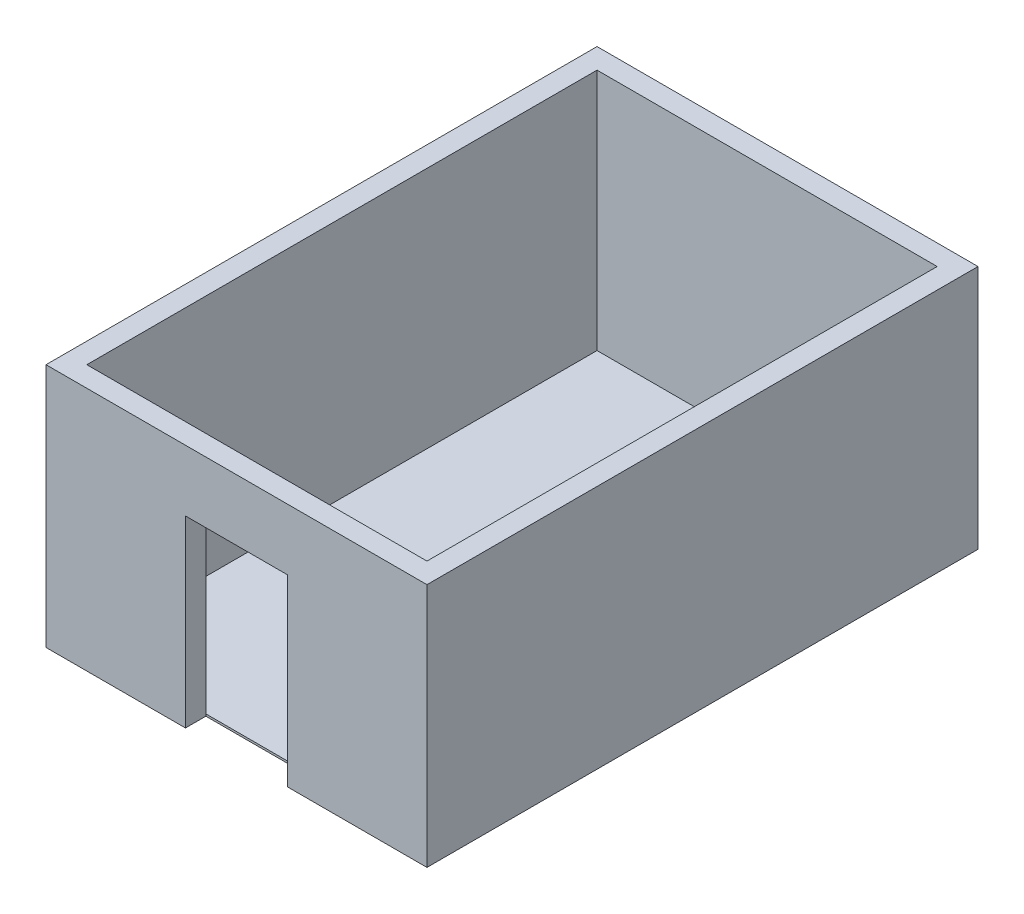
SolidWorks part; units mm, degrees
ref_plane "Front Plane" through (0, 0, 0) normal (0, 0, 1) x (1, 0, 0)
ref_plane "Top Plane" through (0, 0, 0) normal (0, 1, 0) x (1, 0, 0)
ref_plane "Right Plane" through (0, 0, 0) normal (1, 0, 0) x (0, 0, -1)
sketch "Sketch1" plane through (0, 0, 0) normal (0, 1, 0) x (1, 0, 0)
  line L1 (211.6667, -317.5) -> (-211.6667, -317.5)
  line L2 (211.6667, -317.5) -> (211.6667, 317.5)
  line L3 (211.6667, 317.5) -> (-211.6667, 317.5)
  line L4 (-211.6667, -317.5) -> (-211.6667, 317.5)
  line L5 (211.6667, -317.5) -> (-211.6667, 317.5) construction
  line L6 (211.6667, 317.5) -> (-211.6667, -317.5) construction
  point P0 (0, 0)
  dimension "D1" = 423.3333
  dimension "D2" = 635
extrude "Extrude-Thin1" add sketch "Sketch1" along normal blind 304.8 thin thin type one direction wall 25.4
extrude "Boss-Extrude1" add sketch "Sketch1<2>" along normal blind 2.54
sketch "Sketch1<2>" plane through (0, 0, 0) normal (0, 1, 0) x (1, 0, 0) same geometry as "Sketch1"
sketch "Sketch2" plane through (0, 0, 342.9) normal (0, 0, 1) x (1, 0, 0)
  line L0 (-63.5, 0) -> (-63.5, 228.6)
  line L1 (-237.0667, 0) -> (237.0667, 0) construction
  line L2 (-63.5, 228.6) -> (63.5, 228.6)
  line L3 (63.5, 228.6) -> (63.5, 0)
  line L4 (63.5, 0) -> (0, 0) construction
  line L5 (-63.5, 0) -> (0, 0) construction
  line L6 (63.5, 0) -> (-63.5, 0)
  dimension "D1" = 127
  dimension "D2" = 228.6
extrude "Cut-Extrude1" cut sketch "Sketch2" against normal blind 25.4
